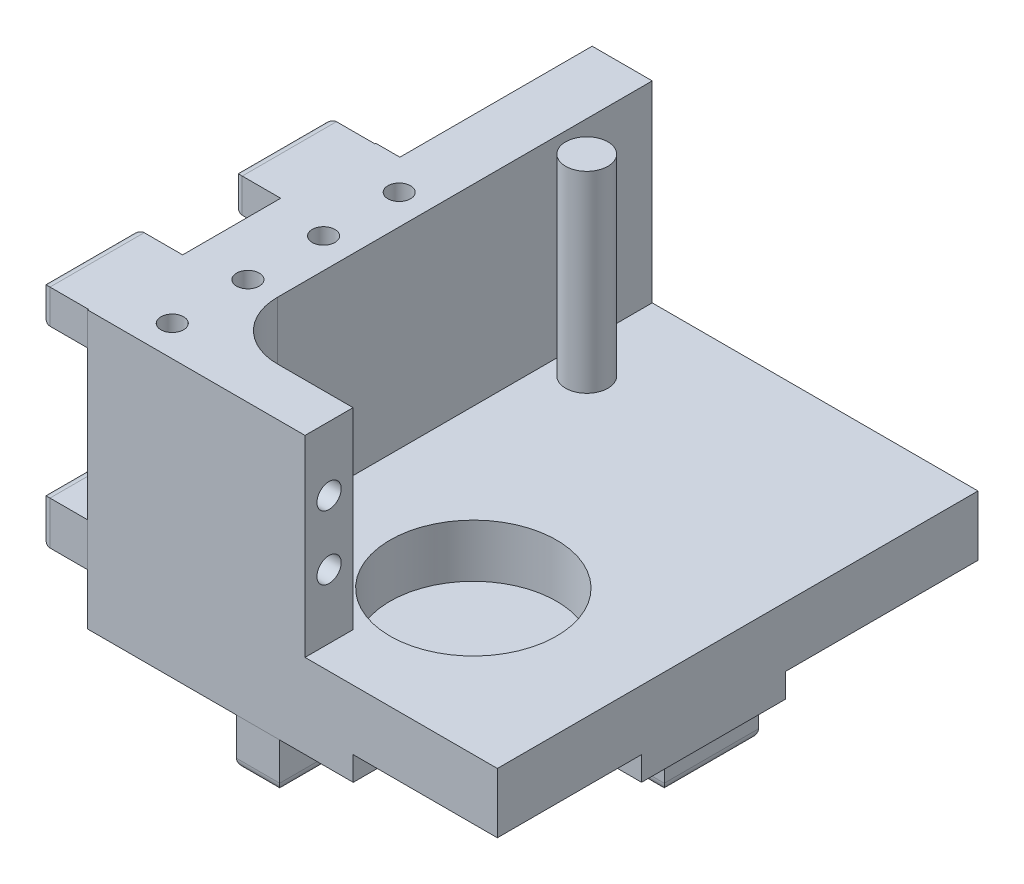
SolidWorks part; units mm, degrees
ref_plane "Front Plane" through (0, 0, 0) normal (0, 0, 1) x (1, 0, 0)
ref_plane "Top Plane" through (0, 0, 0) normal (0, 1, 0) x (1, 0, 0)
ref_plane "Right Plane" through (0, 0, 0) normal (1, 0, 0) x (0, 0, -1)
sketch "Sketch1" plane through (0, 0, 0) normal (0, 1, 0) x (1, 0, 0)
  line L0 (0, 0) -> (22.225, 0) construction
  line L1 (22.225, 19.05) -> (-28.75, 19.05)
  line L2 (22.225, 19.05) -> (22.225, -19.05)
  line L3 (22.225, -19.05) -> (-28.75, -19.05)
  line L4 (-28.75, 19.05) -> (-28.75, -19.05)
  line L5 (15.875, 12.7) -> (-9.525, -12.7) construction
  line L10 (15.875, 12.7) -> (-9.525, 12.7) construction
  line L11 (15.875, 12.7) -> (15.875, -12.7) construction
  line L12 (15.875, -12.7) -> (-9.525, -12.7) construction
  line L13 (-9.525, 12.7) -> (-9.525, -12.7) construction
  line L14 (-34.925, 12.7) -> (-9.525, 12.7) construction
  circle A0 centre (0, 0) radius 11 construction
  point P7 (3.175, 0)
  line B0 (12.875, 6.35) -> (18.875, 6.35)
  line B1 (12.875, 6.35) -> (12.875, 19.05)
  line B2 (12.875, 19.05) -> (18.875, 19.05)
  line B3 (18.875, 6.35) -> (18.875, 19.05)
  line B4 (12.875, 6.35) -> (18.875, 19.05) construction
  line B5 (12.875, 19.05) -> (18.875, 6.35) construction
  line B6 (-12.525, 6.35) -> (-6.525, 6.35)
  line B7 (-12.525, 6.35) -> (-12.525, 19.05)
  line B8 (-6.525, 6.35) -> (-6.525, 19.05)
  line B9 (-12.525, 6.35) -> (-6.525, 19.05) construction
  line B10 (-12.525, 19.05) -> (-6.525, 6.35) construction
  line B11 (-12.525, -19.05) -> (-12.525, -6.35)
  line B12 (-12.525, -6.35) -> (-6.525, -6.35)
  line B13 (-6.525, -19.05) -> (-6.525, -6.35)
  line B14 (-12.525, -19.05) -> (-6.525, -6.35) construction
  line B15 (-12.525, -6.35) -> (-6.525, -19.05) construction
  line B16 (12.875, -19.05) -> (12.875, -6.35)
  line B17 (12.875, -6.35) -> (18.875, -6.35)
  line B18 (18.875, -19.05) -> (18.875, -6.35)
  line B19 (12.875, -19.05) -> (18.875, -6.35) construction
  line B20 (12.875, -6.35) -> (18.875, -19.05) construction
  line B21 (-37.925, 6.35) -> (-31.925, 6.35)
  line B22 (-37.925, 6.35) -> (-37.925, 19.05)
  line B23 (-37.925, 19.05) -> (-31.925, 19.05)
  line B24 (-31.925, 6.35) -> (-31.925, 19.05)
  line B25 (-37.925, 6.35) -> (-31.925, 19.05) construction
  line B26 (-37.925, 19.05) -> (-31.925, 6.35) construction
  line B27 (-37.925, -19.05) -> (-31.925, -19.05)
  line B28 (-37.925, -19.05) -> (-37.925, -6.35)
  line B29 (-37.925, -6.35) -> (-31.925, -6.35)
  line B30 (-31.925, -19.05) -> (-31.925, -6.35)
  line B31 (-37.925, -19.05) -> (-31.925, -6.35) construction
  line B32 (-37.925, -6.35) -> (-31.925, -19.05) construction
  dimension "D2" = 22
  dimension "D1" = 38.1
  dimension "D3" = 25.4
  dimension "D4" = 25.4
  dimension "D5" = 3.175
  dimension "D6" = 22.225
  dimension "D7" = 3.175
sketch_block_instance "SlotGeo-1"
sketch_block "SlotGeo" parameters "D1"=3.1784, "D2"=8.2348
sketch_block_instance "SlotGeo-2"
sketch_block_instance "SlotGeo-3"
sketch_block_instance "SlotGeo-4"
sketch_block_instance "SlotGeo-5"
sketch_block_instance "SlotGeo-6"
extrude "Base" add sketch "Sketch1" along normal blind 7.9375 contours L2 L1 L4 L3
ref_plane "TopBasePlate" through (0, -3.175, 0) normal (0, -1, 0) x (-1, 0, 0)
sketch "Sketch2" plane through (0, 7.9375, 0) normal (0, 1, 0) x (1, 0, 0)
  circle A0 centre (0, 0) radius 11
  dimension "D1" = 22
extrude "Bearing Bore" cut sketch "Sketch2" against normal blind 7 contours A0
sketch "Sketch3" plane through (0, 0.9375, 0) normal (0, 1, 0) x (1, 0, 0)
  circle A0 centre (0, 0) radius 9.525
  dimension "D1" = 19.05
extrude "Thru Hole" [suppressed] cut sketch "Sketch3" against normal through all both and the other way through all
sketch "Sketch4" plane through (0, 7.9375, 0) normal (0, 1, 0) x (1, 0, 0)
  line L0 (22.225, 19.05) -> (-28.75, 19.05) construction
  line L1 (-28.75, -19.05) -> (-20.8125, -19.05)
  line L2 (-28.75, -19.05) -> (-28.75, 19.05)
  line L3 (-28.75, 19.05) -> (-20.8125, 19.05)
  line L4 (-20.8125, -19.05) -> (-20.8125, 19.05)
  dimension "D1" = 7.9375
extrude "Vertical" add sketch "Sketch4" along normal blind 25.4
sketch "Sketch5" plane through (-28.75, 0, 0) normal (-1, 0, 0) x (0, 0, 1)
  line L0 (-12.7, 19.225) -> (12.7, 19.225) construction
  line L1 (12.7, 19.225) -> (12.7, -3.175) construction
  line L3 (-20.955, -3.175) -> (20.955, -3.175) construction
  line L4 (21.5743, -6.175) -> (-23.6916, -6.175) construction
  line L5 (21.5743, -9.175) -> (-23.6916, -9.175) construction
  line L6 (21.5743, -9.175) -> (21.5743, -3.175) construction
  line L7 (21.5743, -3.175) -> (-23.6916, -3.175) construction
  line L8 (-23.6916, -9.175) -> (-23.6916, -3.175) construction
  line B0 (19.05, 16.225) -> (19.05, 22.225)
  line B1 (19.05, 16.225) -> (6.35, 16.225)
  line B2 (6.35, 16.225) -> (6.35, 22.225)
  line B3 (19.05, 22.225) -> (6.35, 22.225)
  line B4 (19.05, 16.225) -> (6.35, 22.225) construction
  line B5 (6.35, 16.225) -> (19.05, 22.225) construction
  line B6 (-6.35, 16.225) -> (-6.35, 22.225)
  line B7 (-6.35, 16.225) -> (-19.05, 16.225)
  line B8 (-6.35, 22.225) -> (-19.05, 22.225)
  line B9 (-6.35, 16.225) -> (-19.05, 22.225) construction
  line B10 (-19.05, 16.225) -> (-6.35, 22.225) construction
  dimension "D1" = 25.4
  dimension "D2" = 6
  dimension "D3" = 25.4
sketch_block_instance "SlotGeo-7"
sketch_block_instance "SlotGeo-8"
sketch "Sketch6" plane through (0, 33.3375, 0) normal (0, 1, 0) x (1, 0, 0)
  line L0 (-24.7812, 14.9904) -> (-24.7812, -14.9904) construction
  line L1 (-28.75, 0) -> (-20.8125, 0) construction
  line L9 (-28.75, 19.05) -> (-28.75, -19.05)
  line L10 (-28.75, -19.05) -> (-20.8125, -19.05)
  line L11 (-20.8125, -19.05) -> (-20.8125, 19.05)
  line L12 (-20.8125, 19.05) -> (-28.75, 19.05)
  line L13 (-28.75, 19.05) -> (-28.75, -19.05) construction
  line L14 (-28.75, -19.05) -> (-20.8125, -19.05) construction
  line L15 (-20.8125, -19.05) -> (-20.8125, 19.05) construction
  line L16 (-20.8125, 19.05) -> (-28.75, 19.05) construction
  circle A0 centre (-24.7812, 14.9904) radius 1.5
  circle A1 centre (-24.7812, 4.9968) radius 1.5
  circle A2 centre (-24.7812, -14.9904) radius 1.5
  circle A3 centre (-24.7812, -4.9968) radius 1.5
  point P6 (-24.7812, 0)
  point P7 (-24.7812, 0)
  dimension "D1" = 3
  dimension "D4" = 3
  dimension "D5" = 3
  dimension "D3" = 29.9808
  dimension "D6" = 9.9936
  dimension "D7" = 19.9872
sketch "Sketch7" plane through (-20.8125, 0, 0) normal (1, 0, 0) x (0, 0, -1)
  line L0 (-19.05, 7.9375) -> (19.05, 7.9375) construction
  line L1 (-19.05, 33.3375) -> (-12.7, 33.3375)
  line L2 (-19.05, 33.3375) -> (-19.05, 7.9375)
  line L3 (-19.05, 7.9375) -> (-12.7, 7.9375)
  line L4 (-12.7, 33.3375) -> (-12.7, 7.9375)
  dimension "D1" = 6.35
extrude "Arm Stop" add sketch "Sketch7" along normal blind 17.6276
sketch "Sketch8" plane through (0, 33.3375, 0) normal (0, 1, 0) x (1, 0, 0)
  line L0 (-3.1849, -12.7) -> (2.1434, -19.05)
  line L1 (22.225, -19.05) -> (-3.1849, -19.05) construction
  line L2 (2.1434, -19.05) -> (-3.1849, -19.05)
  line L3 (-3.1849, -19.05) -> (-3.1849, -12.7)
  dimension "D1" = 40
extrude "Angled Face" [suppressed] add sketch "Sketch8" against normal up to next
fillet "Corner Fillet" radius 7.62 1 edges at (-20.8125, 20.6375, 12.7)
extrude "Top Dowel Holes" cut sketch "Sketch6" against normal blind 7.008
sketch "Sketch13" plane through (-3.1849, 0, 0) normal (1, 0, 0) x (0, 0, -1)
  line L0 (-15.875, 33.3375) -> (-15.875, 7.9375) construction
  line L1 (-12.7, 33.3375) -> (-19.05, 33.3375) construction
  line L2 (-19.05, 7.9375) -> (-12.7, 7.9375) construction
  circle A0 centre (-15.875, 24.8708) radius 1.6
  circle A1 centre (-15.875, 16.4042) radius 1.6
  dimension "D2" = 3.2
  dimension "D3" = 3.2
  dimension "D4" = 8.4667
  dimension "D1" = 25.4
  dimension "D5" = 16.9333
extrude "Stopper Dowel Holes" cut sketch "Sketch13" against normal blind 10.46
sketch "Sketch14" plane through (0, 0, 0) normal (0, -1, 0) x (1, 0, 0)
  line L0 (-28.75, 19.05) -> (3.1877, 19.05)
  line L1 (22.225, 19.05) -> (-28.75, 19.05) construction
  line L2 (3.1877, 19.05) -> (3.1877, 0)
  line L3 (3.1877, 0) -> (22.225, 0)
  line L4 (22.225, -19.05) -> (22.225, 19.05) construction
  line L5 (22.225, 0) -> (22.225, -19.05)
  line L6 (22.225, -19.05) -> (-28.75, -19.05)
  line L7 (-28.75, -19.05) -> (-28.75, 19.05)
  dimension "D1" = 19.0373
  dimension "D2" = 19.05
extrude "Base Contact" add sketch "Sketch14" along normal up to surface (3.175 mm away) up to plane "TopBasePlate"
sketch "Sketch15" plane through (0, -3.175, 0) normal (0, -1, 0) x (1, 0, 0)
  line L0 (-28.75, 19.05) -> (-28.75, -19.05) construction
  line L1 (-12.367, 18.923) -> (-6.652, 18.923)
  line L2 (-12.367, 18.923) -> (-12.367, 6.477)
  line L3 (-12.367, 6.477) -> (-6.652, 6.477)
  line L4 (-6.652, 18.923) -> (-6.652, 6.477)
  line L5 (-12.367, 18.923) -> (-6.652, 6.477) construction
  line L6 (-12.367, 6.477) -> (-6.652, 18.923) construction
  line L7 (-12.367, -6.477) -> (-6.652, -6.477)
  line L8 (-12.367, -6.477) -> (-12.367, -18.923)
  line L9 (-12.367, -18.923) -> (-6.652, -18.923)
  line L10 (-6.652, -6.477) -> (-6.652, -18.923)
  line L11 (-12.367, -6.477) -> (-6.652, -18.923) construction
  line L12 (-12.367, -18.923) -> (-6.652, -6.477) construction
  line L13 (13.033, -6.477) -> (18.748, -6.477)
  line L14 (13.033, -6.477) -> (13.033, -18.923)
  line L15 (13.033, -18.923) -> (18.748, -18.923)
  line L16 (18.748, -6.477) -> (18.748, -18.923)
  line L17 (13.033, -6.477) -> (18.748, -18.923) construction
  line L18 (13.033, -18.923) -> (18.748, -6.477) construction
  line L19 (3.1877, 19.05) -> (-28.75, 19.05) construction
  point P0 (-9.5095, 12.7)
  point P5 (-9.5095, -12.7)
  point P10 (15.8905, -12.7)
  dimension "D1" = 5.715
  dimension "D2" = 12.446
  dimension "D3" = 12.446
  dimension "D4" = 5.715
  dimension "D5" = 5.715
  dimension "D6" = 12.446
  dimension "D7" = 16.383
  dimension "D8" = 12.954
  dimension "D9" = 0.127
  dimension "D10" = 19.685
extrude "Bottom Tabs" add sketch "Sketch15" along normal blind 6.35
fillet "Tab Fillet" radius 1.27 12 edges at (15.8905, -9.525, -18.923) (13.033, -9.525, -12.7) (15.8905, -9.525, -6.477) (18.748, -9.525, -12.7) (-9.5095, -9.525, 6.477) (-12.367, -9.525, 12.7) (-9.5095, -9.525, 18.923) (-6.652, -9.525, 12.7) (-9.5095, -9.525, -18.923) (-12.367, -9.525, -12.7) (-9.5095, -9.525, -6.477) (-6.652, -9.525, -12.7)
sketch "Sketch16" plane through (-28.75, 0, 0) normal (-1, 0, 0) x (0, 0, 1)
  line L0 (19.05, 33.3375) -> (19.05, -3.175) construction
  line L1 (-19.05, 33.3375) -> (19.05, 33.3375)
  line L2 (-19.05, 33.3375) -> (-19.05, -3.175)
  line L3 (-19.05, -3.175) -> (19.05, -3.175)
  line L4 (19.05, 33.3375) -> (19.05, -3.175)
  line L5 (19.05, -3.175) -> (-19.05, -3.175) construction
extrude "Boss-Extrude3" add sketch "Sketch16" along normal blind 3.175
sketch "Sketch18" plane through (-31.925, 0, 0) normal (-1, 0, 0) x (0, 0, 1)
  line L0 (19.05, 33.3375) -> (-19.05, 33.3375) construction
  line L1 (-18.923, 3.4798) -> (-6.477, 3.4798)
  line L2 (-18.923, 3.4798) -> (-18.923, 9.1948)
  line L3 (-18.923, 9.1948) -> (-6.477, 9.1948)
  line L4 (-6.477, 3.4798) -> (-6.477, 9.1948)
  line L5 (-18.923, 3.4798) -> (-6.477, 9.1948) construction
  line L6 (-18.923, 9.1948) -> (-6.477, 3.4798) construction
  line L7 (6.477, 3.4798) -> (18.923, 3.4798)
  line L8 (6.477, 3.4798) -> (6.477, 9.1948)
  line L9 (6.477, 9.1948) -> (18.923, 9.1948)
  line L10 (18.923, 3.4798) -> (18.923, 9.1948)
  line L11 (6.477, 3.4798) -> (18.923, 9.1948) construction
  line L12 (6.477, 9.1948) -> (18.923, 3.4798) construction
  line L13 (-18.923, 33.3375) -> (-6.477, 33.3375)
  line L14 (-18.923, 33.3375) -> (-18.923, 28.8544)
  line L15 (-18.923, 28.8544) -> (-6.477, 28.8544)
  line L16 (-6.477, 33.3375) -> (-6.477, 28.8544)
  line L17 (-18.923, 33.3375) -> (-6.477, 28.8544) construction
  line L18 (-18.923, 28.8544) -> (-6.477, 33.3375) construction
  line L19 (6.477, 33.3375) -> (18.923, 33.3375)
  line L20 (6.477, 33.3375) -> (6.477, 28.8544)
  line L21 (6.477, 28.8544) -> (18.923, 28.8544)
  line L22 (18.923, 33.3375) -> (18.923, 28.8544)
  line L23 (6.477, 33.3375) -> (18.923, 28.8544) construction
  line L24 (6.477, 28.8544) -> (18.923, 33.3375) construction
  line L25 (19.05, -3.175) -> (19.05, 33.3375) construction
  line L26 (-19.05, 33.3375) -> (-19.05, -3.175) construction
  line L27 (-19.05, -3.175) -> (19.05, -3.175) construction
  point P0 (-12.7, 6.3373)
  point P5 (12.7, 6.3373)
  point P10 (-12.7, 31.096)
  point P15 (12.7, 31.096)
  dimension "D1" = 5.715
  dimension "D2" = 5.715
  dimension "D3" = 12.446
  dimension "D4" = 12.446
  dimension "D5" = 0.127
  dimension "D6" = 0.127
  dimension "D7" = 6.6548
  dimension "D8" = 19.6596
extrude "Boss-Extrude4" add sketch "Sketch18" along normal blind 6.35
fillet "Fillet3" radius 1.27 16 edges at (-38.275, 3.4798, -12.7) (-38.275, 6.3373, -18.923) (-38.275, 9.1948, -12.7) (-38.275, 6.3373, -6.477) (-38.275, 3.4798, 12.7) (-38.275, 6.3373, 6.477) (-38.275, 9.1948, 12.7) (-38.275, 6.3373, 18.923) (-38.275, 28.8544, 12.7) (-38.275, 31.096, 6.477) (-38.275, 33.3375, 12.7) (-38.275, 31.096, 18.923) (-38.275, 28.8544, -12.7) (-38.275, 31.096, -18.923) (-38.275, 33.3375, -12.7) (-38.275, 31.096, -6.477)
sketch "Sketch11" plane through (0, 0, -19.05) normal (0, 0, -1) x (-1, 0, 0)
  line L0 (-22.225, 7.9375) -> (20.8125, 7.9375)
  line L1 (20.8125, 7.9375) -> (20.8125, 33.3375)
  line L2 (20.8125, 33.3375) -> (31.925, 33.3375) construction
  line L3 (20.8125, 33.3375) -> (28.75, 33.3375)
  line L4 (28.75, 33.3375) -> (28.75, 0)
  line L5 (28.75, 0) -> (-22.225, 0)
  line L6 (-22.225, 0) -> (-22.225, 7.9375)
extrude "Spring Base" add sketch "Sketch11" along normal blind 25.4
sketch "Sketch12" plane through (0, 7.9375, 0) normal (0, 1, 0) x (1, 0, 0)
  line L0 (-16.7612, 44.45) -> (-16.7612, 31.75) construction
  line L1 (-20.8125, 44.45) -> (22.225, 44.45) construction
  line L2 (-20.8125, -5.08) -> (-20.8125, 44.45) construction
  circle A0 centre (-16.7612, 31.75) radius 2.794
  dimension "D3" = 5.588
  dimension "D1" = 4.0513
  dimension "D2" = 12.7
extrude "Spring Mount" add sketch "Sketch12" along normal blind 25.4 contours A0
equation "\"D4@Sketch6\"=\"D1@Sketch6\""
equation "\"D5@Sketch6\"=\"D1@Sketch6\""
equation "\"D6@Sketch6\"=\"D3@Sketch6\"/3"
equation "\"D7@Sketch6\"=2*\"D3@Sketch6\"/3"
